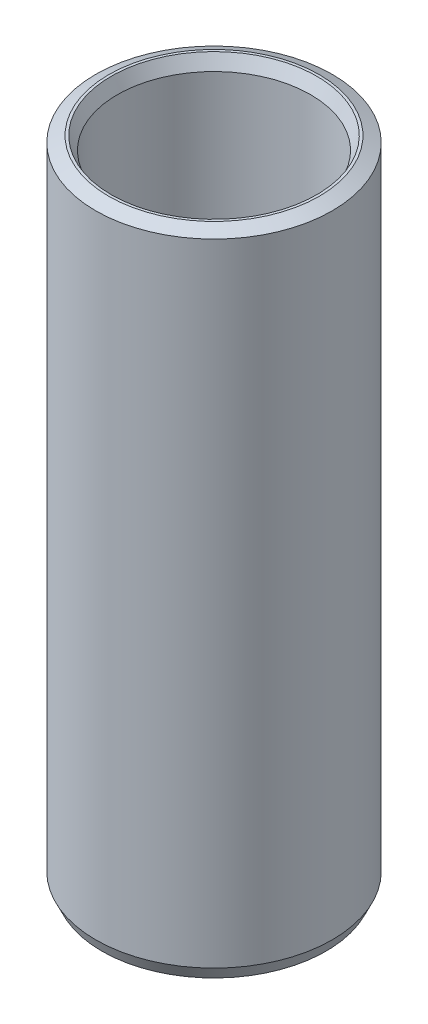
SolidWorks part; units mm, degrees
ref_plane "Front Plane" through (0, 0, 0) normal (0, 0, 1) x (1, 0, 0)
ref_plane "Top Plane" through (0, 0, 0) normal (0, 1, 0) x (1, 0, 0)
ref_plane "Right Plane" through (0, 0, 0) normal (1, 0, 0) x (0, 0, -1)
sketch "Sketch1" plane through (0, 0, 0) normal (0, 1, 0) x (1, 0, 0)
  circle A0 centre (0, 0) radius 37.5
  dimension "SLEEVE_OD" = 75
extrude "Boss-Extrude1" add sketch "Sketch1" along normal blind 206.2508
sketch "Sketch2" plane through (0, 0, 0) normal (0, 1, 0) x (1, 0, 0)
  circle A0 centre (0, 0) radius 30.629
  dimension "BORE_D" = 61.258
extrude "Cut-Extrude1" cut sketch "Sketch2" along normal through all
chamfer "Chamfer1" distance 1.9499 angle 64.546 4 edges at (0, 206.2508, 30.629) (0, 0, 30.629) (0, 0, 37.5) (0, 206.2508, 37.5) first distance on face at (0, 206.2508, 30.629) first distance on face at (0, 0, 30.629) first distance on face at (0, 206.2508, 37.5)
